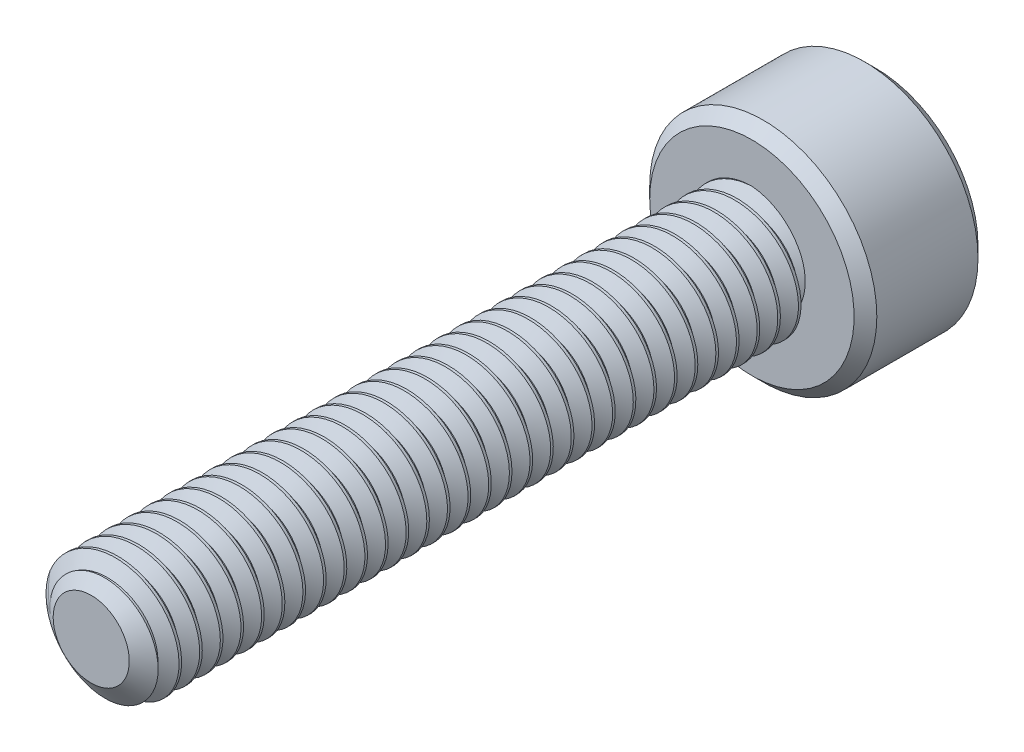
SolidWorks part; units mm, degrees
material "Plain Carbon Steel"
ref_plane "Front Plane" through (0, 0, 0) normal (0, 0, 1) x (1, 0, 0)
ref_plane "Top Plane" through (0, 0, 0) normal (0, 1, 0) x (1, 0, 0)
ref_plane "Right Plane" through (0, 0, 0) normal (1, 0, 0) x (0, 0, -1)
sketch "Sketch1" plane through (0, 0, 0) normal (0, 0, 1) x (1, 0, 0)
  circle A0 centre (0, 0) radius 1.5
  dimension "OD" = 3
extrude "Extrude1" add sketch "Sketch1" against normal blind 16
sketch "Sketch2" plane through (0, 0, 0) normal (0, 0, 1) x (1, 0, 0)
  circle A0 centre (0, 0) radius 1.5 construction
  circle A1 centre (0, 0) radius 1.5
curve "Helix/Spiral1" pitch 0.5 height 16.5 turns 33 parameters "pitch"=0.5
sketch "Sketch3" plane through (0, 0, 0) normal (1, 0, 0) x (0, 0, -1)
  line L0 (-0.4375, 1.5) -> (-0.25, 1.1752)
  line L1 (-0.25, 1.1752) -> (-0.1875, 1.1752)
  line L2 (-0.1875, 1.1752) -> (0, 1.5)
  line L3 (-0.4375, 1.5) -> (0, 1.5)
  line L4 (-0.2187, 1.5) -> (-0.2187, 1.1752) construction
  line L5 (-0.3438, 1.3376) -> (-0.0937, 1.3376) construction
  line L6 (0, 1.5) -> (0, -1.5) construction
  dimension "D1" = 0.0625
  dimension "D2" = 0.25
  dimension "D3" = 60
sweep "Cut-Sweep1" cut profiles "Sketch3" path "Helix/Spiral1" align with end faces yes
sketch "Sketch4" plane through (0, 0, 0) normal (1, 0, 0) x (0, 0, -1)
  line L0 (0.4053, 1.5) -> (0, 0.9212)
  line L1 (0, 0.9212) -> (0, 1.5)
  line L2 (0.4053, 1.5) -> (0, 1.5)
  line L3 (-0.4375, 1.5) -> (0, 1.5) construction
  line L4 (0, 0) -> (7.0209, 0) construction
  dimension "D1" = 55
  dimension "D2" = 0.254
revolve "Cut-Revolve1" cut sketch "Sketch4" angle 360 about L4
sketch "Sketch6" plane through (0, 0, -16) normal (0, 0, -1) x (-1, 0, 0)
  circle A0 centre (0, 0) radius 2.75
  dimension "head dia" = 5.5
extrude "Extrude2" add sketch "Sketch6" along normal blind 3
sketch "Sketch7" plane through (0, 0, -19) normal (0, 0, -1) x (-1, 0, 0)
  line L1 (0, 1.4434) -> (-1.25, 0.7217)
  line L2 (-1.25, 0.7217) -> (-1.25, -0.7217)
  line L3 (-1.25, -0.7217) -> (0, -1.4434)
  line L4 (0, -1.4434) -> (1.25, -0.7217)
  line L5 (1.25, -0.7217) -> (1.25, 0.7217)
  line L6 (1.25, 0.7217) -> (0, 1.4434)
  circle A0 centre (0, 0) radius 1.25 construction
  dimension "hex dia" = 2.5
extrude "Cut-Extrude1" cut sketch "Sketch7" against normal blind 1.875
sketch "Sketch8" plane through (0, 0, -19) normal (0, 0, -1) x (-1, 0, 0)
  circle A0 centre (0, 0) radius 1.4434
extrude "Cut-Extrude2" cut sketch "Sketch8" against normal through all draft 45
chamfer "Chamfer1" distance 0.275 angle 45 2 edges at (-2.75, 0, -19) (-2.75, 0, -16)
sketch "Sketch9" plane through (0, 0, 0) normal (1, 0, 0) x (0, 0, -1)
  line L0 (0, 1.5) -> (0, -1.5) construction
  line L1 (2.75, 1.5) -> (2.75, -1.5) construction
  dimension "D1" = 2.75
equation "\"D3@Helix/Spiral1\" = \"screw length@Extrude1\"+\"pitch@Helix/Spiral1\""
equation "\"D1@Sketch3\" = \"pitch@Helix/Spiral1\"*.125"
equation "\"D2@Sketch3\" = \"pitch@Helix/Spiral1\"*.5"
equation "\"D1@Cut-Extrude1\" = \"hex dia@Sketch7\"*.75"
equation "\"D1@Chamfer1\" = \"head dia@Sketch6\"*.05"
equation "\"D1@Sketch9\" = \"pitch@Helix/Spiral1\"*5.5"
